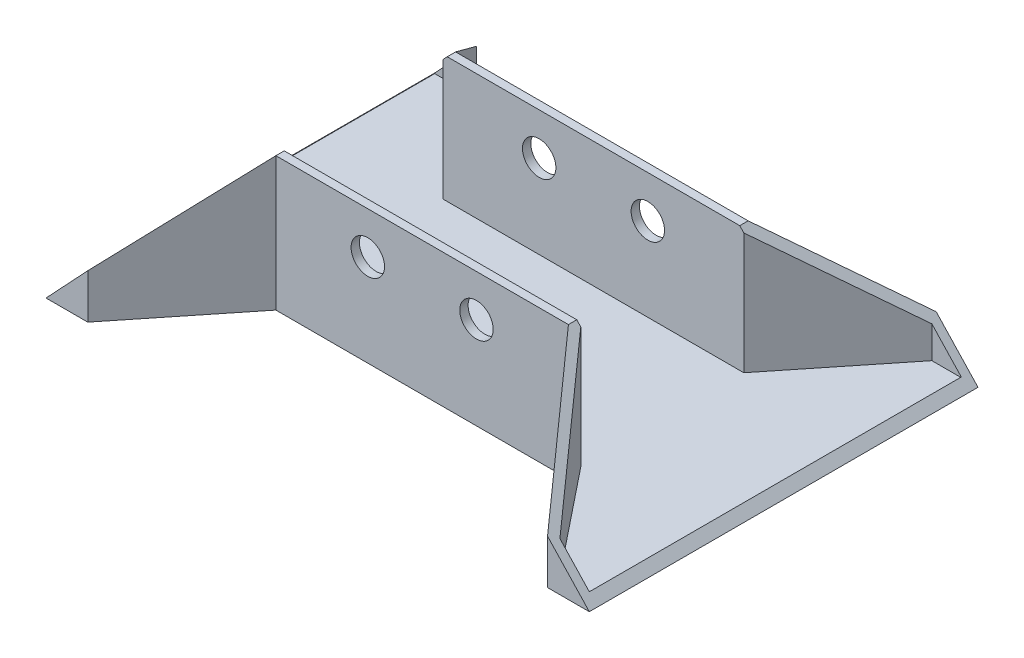
SolidWorks part; units mm, degrees
ref_plane "正面" through (0, 0, 0) normal (0, 0, 1) x (1, 0, 0)
ref_plane "平面" through (0, 0, 0) normal (0, 1, 0) x (1, 0, 0)
ref_plane "右側面" through (0, 0, 0) normal (1, 0, 0) x (0, 0, -1)
sketch "ｽｹｯﾁ1" plane through (0, 0, 0) normal (0, 0, 1) x (1, 0, 0)
  line L0 (-65, 0) -> (65, 0)
  line L1 (65, 0) -> (35, 32)
  line L2 (35, 32) -> (-35, 32)
  line L3 (-35, 32) -> (-65, 0)
  point P4 (0, 0)
  dimension "D1" = 130
  dimension "D2" = 30
  dimension "D3" = 30
  dimension "D4" = 32
extrude "ﾎﾞｽ - 押し出し1" add sketch "ｽｹｯﾁ1" along normal mid plane 93
sketch "Base-W" plane through (0, 32, 0) normal (0, 1, 0) x (1, 0, 0)
  line L0 (-55, -46.5) -> (-35, -21.5)
  line L1 (0, 21.5) -> (0, -21.5) construction
  line L2 (-35, -46.5) -> (-35, 46.5) construction
  line L3 (-35, -21.5) -> (35, -21.5)
  line L4 (35, -46.5) -> (35, 46.5) construction
  line L5 (35, -21.5) -> (55, -46.5)
  line L6 (65, -46.5) -> (35, -46.5) construction
  line L7 (55, -46.5) -> (-55, -46.5)
  line L8 (-55, 46.5) -> (-35, 21.5)
  line L9 (-35, 46.5) -> (-65, 46.5) construction
  line L10 (-35, 21.5) -> (35, 21.5)
  line L11 (35, 21.5) -> (55, 46.5)
  line L12 (65, 46.5) -> (35, 46.5) construction
  line L13 (55, 46.5) -> (-55, 46.5)
  line L14 (65, -46.5) -> (65, 46.5) construction
  line L15 (-65, -46.5) -> (-65, 46.5) construction
  line L16 (-35, -46.5) -> (-65, -46.5) construction
  point P27 (0, 21.5)
  point P29 (0, 0)
  dimension "D1" = 10
  dimension "D2" = 10
  dimension "D3" = 43
  dimension "D5" = 10
  dimension "D6" = 10
extrude "ｶｯﾄ - 押し出し1" cut sketch "Base-W" against normal through all
sketch "Base-t" plane through (0, 32, 0) normal (0, 1, 0) x (1, 0, 0)
  line L24 (-35.9612, -19.5) -> (35.9612, -19.5)
  line L25 (-55.9612, -44.5) -> (-35.9612, -19.5)
  line L26 (-63, -44.5) -> (-55.9612, -44.5)
  line L27 (-63, 44.5) -> (-63, -44.5)
  line L28 (-55.9612, 44.5) -> (-63, 44.5)
  line L29 (-35.9612, 19.5) -> (-55.9612, 44.5)
  line L30 (35.9612, 19.5) -> (-35.9612, 19.5)
  line L31 (55.9612, 44.5) -> (35.9612, 19.5)
  line L32 (63, 44.5) -> (55.9612, 44.5)
  line L33 (63, -44.5) -> (63, 44.5)
  line L34 (55.9612, -44.5) -> (63, -44.5)
  line L35 (35.9612, -19.5) -> (55.9612, -44.5)
  line L36 (-35.9612, -19.5) -> (35.9612, -19.5)
  line L37 (-55.9612, -44.5) -> (-35.9612, -19.5)
  line L38 (-63, -44.5) -> (-55.9612, -44.5)
  line L39 (-63, 44.5) -> (-63, -44.5)
  line L40 (-55.9612, 44.5) -> (-63, 44.5)
  line L41 (-35.9612, 19.5) -> (-55.9612, 44.5)
  line L42 (35.9612, 19.5) -> (-35.9612, 19.5)
  line L43 (55.9612, 44.5) -> (35.9612, 19.5)
  line L44 (63, 44.5) -> (55.9612, 44.5)
  line L45 (63, -44.5) -> (63, 44.5)
  line L46 (55.9612, -44.5) -> (63, -44.5)
  line L47 (35.9612, -19.5) -> (55.9612, -44.5)
  dimension "D1" = 2
extrude "ｶｯﾄ - 押し出し2" cut sketch "Base-t" against normal offset from surface (30 mm away) 2 up to face at (0, 0, 0)
sketch "ｽｹｯﾁ4" plane through (0, 0, 21.5) normal (0, 0, 1) x (1, 0, 0)
  line L0 (35, 32) -> (-35, 32) construction
  circle A0 centre (-13, 22) radius 4
  circle A1 centre (13, 22) radius 4
  dimension "D1" = 8
  dimension "D2" = 10
  dimension "D3" = 13
  dimension "D4" = 13
extrude "ｶｯﾄ - 押し出し3" cut sketch "ｽｹｯﾁ4" against normal through all
